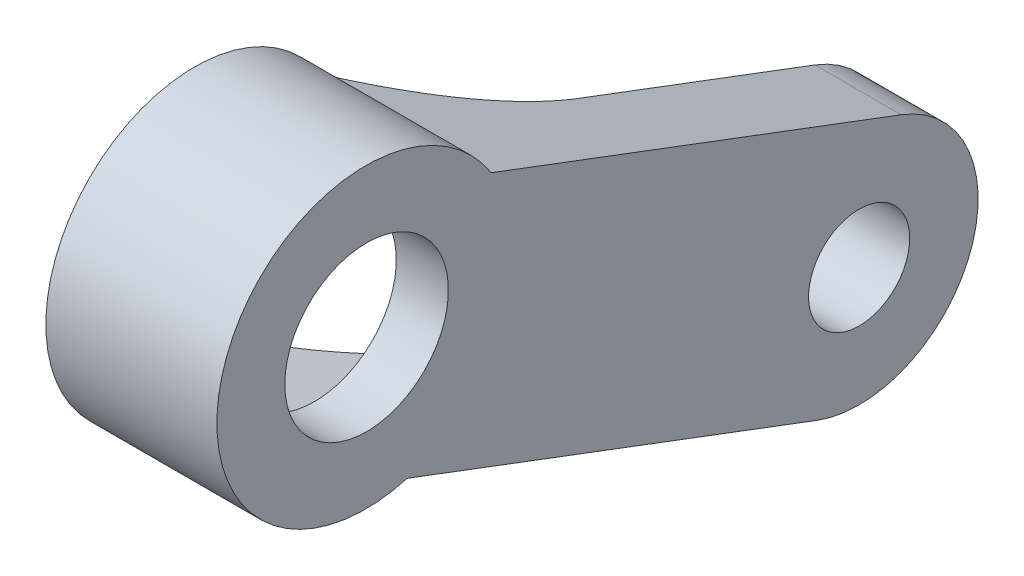
SolidWorks part; units mm, degrees
ref_plane "Front Plane" through (0, 0, 0) normal (0, 0, 1) x (1, 0, 0)
ref_plane "Top Plane" through (0, 0, 0) normal (0, 1, 0) x (1, 0, 0)
ref_plane "Right Plane" through (0, 0, 0) normal (1, 0, 0) x (0, 0, -1)
ref_plane "Plane1" through (38.55, 0, 0) normal (-1, 0, 0) x (0, -1, 0)
sketch "Sketch1" plane through (38.55, 0, 0) normal (-1, 0, 0) x (0, -1, 0)
  circle A2 centre (23.2827, -61.5595) radius 5
  dimension "D1" = 10
extrude "Boss-Extrude1" add sketch "Sketch1" against normal blind 2.85
draft "Draft1" [suppressed] type of draft neutral plane draft angle 45 faces to draft 1 reverse direction yes parameters "D1"=45
sketch "Sketch2" plane through (41.4, 0, 0) normal (1, 0, 0) x (0, 0, -1)
  line L0 (63.0044, -19.5527) -> (79.5617, -25.8027)
  line L1 (76.7365, -33.2872) -> (60.1792, -27.0372)
  arc A0 (79.5617, -25.8027) -> (76.7365, -33.2872) centre (78.1491, -29.5449) cw
  arc A1 (60.1792, -27.0372) -> (63.0044, -19.5527) centre (61.5918, -23.2949) cw
extrude "Boss-Extrude2" add sketch "Sketch2" along normal blind 2.9
extrude "Boss-Extrude3" add sketch "Sketch1<2>" against normal up to surface (5.75 mm away) up to face at (44.3, -26.4199, -69.8704)
sketch "Sketch1<2>" plane through (38.55, 0, 0) normal (-1, 0, 0) x (0, -1, 0) same geometry as "Sketch1"
hole_wizard "Hole1" positions "Sketch4" profile "Sketch3" legacy
sketch "Sketch4" plane through (44.3, 0, 0) normal (1, 0, 0) x (0, 0, -1)
  point P0 (78.1491, -29.5449)
sketch "Sketch3" plane through (44.3, -29.5449, -78.1491) normal (0, 1, 0) x (0, 0, -1)
  line L0 (0, 0) -> (0, 5.75)
  line L1 (0, 5.75) -> (1.7, 5.75)
  line L2 (1.7, 5.75) -> (1.7, 0)
  line L3 (1.7, 0) -> (0, 0)
  line L4 (0, 110) -> (0, -10) construction
  dimension "Diameter" = 3.4
  dimension "Depth" = 5.75
hole_wizard "Hole2" positions "Sketch6" profile "Sketch5" legacy end condition through all
sketch "Sketch6" plane through (38.55, 0, 0) normal (-1, 0, 0) x (0, 0, 1)
  point P0 (-61.5918, -23.2949)
sketch "Sketch5" plane through (38.55, -23.2949, -61.5918) normal (0, 1, 0) x (0, 0, 1)
  line L0 (0, 0) -> (0, 5.75)
  line L1 (0, 5.75) -> (2.75, 5.75)
  line L2 (2.75, 5.75) -> (2.75, 2.8)
  line L3 (2.75, 2.8) -> (2.2, 2.8)
  line L4 (2.2, 2.8) -> (2.2, 0)
  line L5 (2.2, 0) -> (0, 0)
  line L6 (0, 110) -> (0, -10) construction
  dimension "Diameter" = 5.5
  dimension "Depth" = 5.75
  dimension "C-Bore Diameter" = 4.4
  dimension "C-Bore Depth" = 2.8
chamfer "Chamfer1" distance 0.5 angle 45 1 edges at (38.55, -23.2949, -59.3918)
fillet "Fillet1" radius 6 1 edges at (41.4, -25.0485, -66.2373) tangent propagation no
sketch "Sketch7" plane through (38.55, 0, 0) normal (-1, 0, 0) x (0, 0, 1)
  line L0 (-61.5918, -23.2949) -> (-78.1491, -29.5449) construction
  line L1 (-60.8094, -26.9113) -> (-69.1643, -28.7187)
  line L2 (-69.1643, -28.7187) -> (-70.8594, -24.2279)
  line L3 (-70.8594, -24.2279) -> (-63.3943, -20.0637)
  arc A0 (-60.8094, -26.9113) -> (-63.3943, -20.0637) centre (-61.5918, -23.2949) ccw
  point P8 (-70.0119, -26.4733)
  dimension "D1" = 7.4
  dimension "D2" = 9
  dimension "D3" = 4.8
extrude "Cut-Extrude1" cut sketch "Sketch7" against normal blind 4
